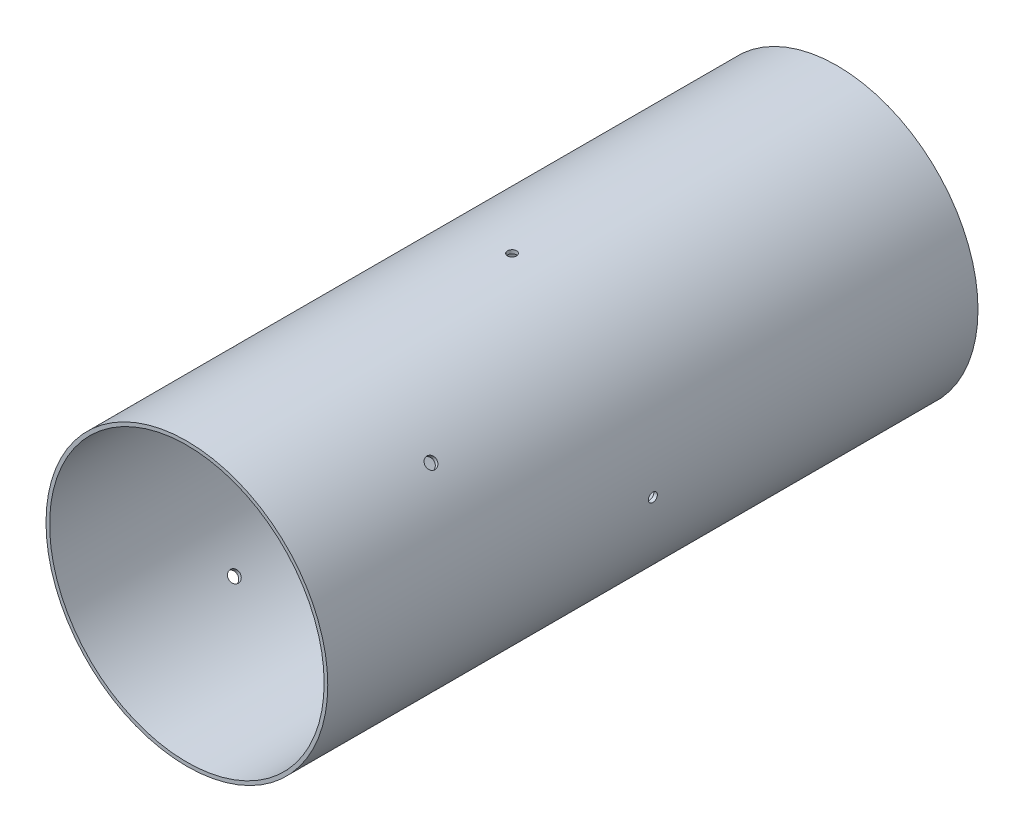
SolidWorks part; units mm, degrees
ref_plane "Front Plane" through (0, 0, 0) normal (0, 0, 1) x (1, 0, 0)
ref_plane "Top Plane" through (0, 0, 0) normal (0, 1, 0) x (1, 0, 0)
ref_plane "Right Plane" through (0, 0, 0) normal (1, 0, 0) x (0, 0, -1)
sketch "Sketch1" plane through (0, 0, 0) normal (0, 0, 1) x (1, 0, 0)
  circle A0 centre (0, 0) radius 49.53
  circle A1 centre (0, 0) radius 48.26
  dimension "D1" = 99.06
  dimension "D2" = 96.52
extrude "Boss-Extrude1" add sketch "Sketch1" along normal blind 228.6
extrude "Cut-Extrude1" cut sketch "Sketch2" against normal blind 12.7
sketch "Sketch2" plane through (-120.5803, -48.7382, -78.9954) normal (-0.7071, 0.7071, 0) x (0.7071, 0.7071, 0)
  circle A0 centre (119.7263, -256.7954) radius 1.9844
pattern_circular "CirPattern1" count 4 over 360 of "Cut-Extrude1"
extrude "Cut-Extrude2" cut sketch "Sketch3" against normal blind 25.4
sketch "Sketch3" plane through (-108.0218, -85.4992, -79.3332) normal (-0.866, 0.5, 0) x (0, 0, 1)
  circle A0 centre (196.8082, 128.0554) radius 2.3813
  circle A1 centre (190.4582, 128.0554) radius 2.3813
  point P3 (0, 0)
  point P6 (0, 0)
  point P8 (0, 0)
extrude "Cut-Extrude3" cut sketch "Sketch4" against normal blind 37.338
sketch "Sketch4" plane through (-33.6632, -130.5648, -80.7782) normal (1, 0, 0) x (0, 0, -1)
  circle A0 centre (-195.0782, 130.5648) radius 1.5875
  point P2 (0, 0)
  point P3 (-80.7782, 130.5648)
  point P4 (-195.0782, 181.3648)
pattern_circular "CirPattern2" count 4 over 360 about axis through (0, 0, 228.6) along (0, 0, -1) of "Cut-Extrude3" reverse direction yes
